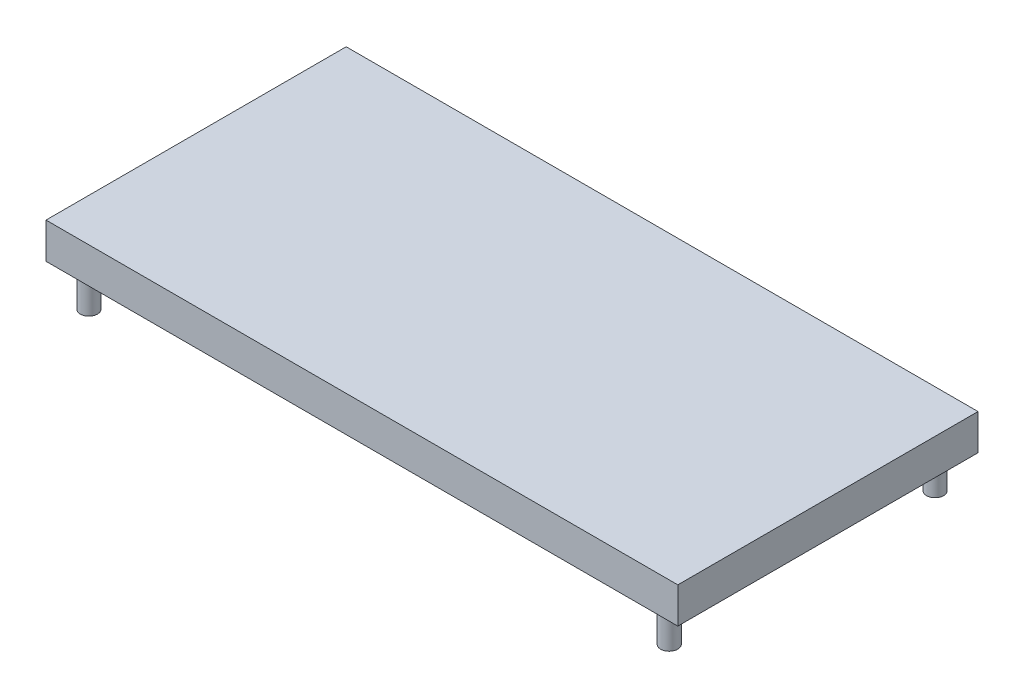
SolidWorks part; units mm, degrees
ref_plane "Front Plane" through (0, 0, 0) normal (0, 0, 1) x (1, 0, 0)
ref_plane "Top Plane" through (0, 0, 0) normal (0, 1, 0) x (1, 0, 0)
ref_plane "Right Plane" through (0, 0, 0) normal (1, 0, 0) x (0, 0, -1)
sketch "Sketch2" plane through (0, 0, 0) normal (0, 1, 0) x (1, 0, 0)
  line L1 (-110.5, 52.5) -> (110.5, 52.5)
  line L2 (-110.5, 52.5) -> (-110.5, -52.5)
  line L3 (-110.5, -52.5) -> (110.5, -52.5)
  line L4 (110.5, 52.5) -> (110.5, -52.5)
  dimension "D1" = 221
  dimension "D2" = 105
  dimension "D3" = 110.5
  dimension "D4" = 52.5
extrude "Boss-Extrude1" add sketch "Sketch2" along normal blind 2.5
sketch "Sketch3" plane through (0, 0, 0) normal (0, -1, 0) x (1, 0, 0)
  line L13 (110.5, -52.5) -> (-110.5, -52.5)
  line L14 (110.5, -52.5) -> (110.5, 52.5)
  line L15 (110.5, 52.5) -> (-110.5, 52.5)
  line L16 (-108, 50) -> (-108, -50)
  line L17 (108, 50) -> (-108, 50)
  line L18 (-108, -50) -> (108, -50)
  line L19 (108, -50) -> (108, 50)
  line L20 (-108, 50) -> (-108, -50)
  line L21 (108, 50) -> (-108, 50)
  line L22 (-108, -50) -> (108, -50)
  line L23 (108, -50) -> (108, 50)
  line L24 (-110.5, -52.5) -> (-110.5, 52.5)
  dimension "D1" = 2.5
extrude "Boss-Extrude2" add sketch "Sketch3" along normal blind 10
sketch "Sketch5" plane through (0, 0, 0) normal (0, -1, 0) x (1, 0, 0)
  line L0 (6.875, 0) -> (-6.875, 0) construction
  line L1 (101.5, -46.5) -> (-101.5, -46.5) construction
  line L2 (101.5, -46.5) -> (101.5, 46.5) construction
  line L3 (101.5, 46.5) -> (-101.5, 46.5) construction
  line L4 (-101.5, -46.5) -> (-101.5, 46.5) construction
  line L5 (0, -6.875) -> (0, 6.875) construction
  circle A0 centre (101.5, -46.5) radius 3
  circle A1 centre (-101.5, -46.5) radius 3
  circle A2 centre (-101.5, 46.5) radius 3
  circle A3 centre (101.5, 46.5) radius 3
  dimension "D5" = 6
  dimension "D1" = 203
  dimension "D2" = 93
  dimension "D3" = 46.5
  dimension "D4" = 101.5
extrude "Boss-Extrude3" add sketch "Sketch5" along normal blind 23
hole_wizard "M3 Tapped Hole1" positions "Sketch6" profile "Sketch7" tap size "M3" standard "ISO"
sketch "Sketch6" plane through (0, -23, 0) normal (0, -1, 0) x (-1, 0, 0)
  point P0 (-101.5, 46.5)
  point P3 (101.5, 46.5)
  point P6 (101.5, -46.5)
  point P9 (-101.5, -46.5)
sketch "Sketch7" plane through (101.5, -23, -46.5) normal (1, 0, 0) x (0, 0, -1)
  line L0 (0, 0) -> (0, 10.8511)
  line L1 (0, 10.8511) -> (1.25, 10.1)
  line L2 (1.25, 10.1) -> (1.25, 0)
  line L5 (1.25, 0) -> (0, 0)
  line L10 (0, 10.8511) -> (-1.25, 10.1) construction
  line L11 (0, -6.35) -> (0, 107.95) construction
  dimension "Tap Drill Dia." = 2.5
  dimension "Tap Drill Depth" = 10.1
  dimension "Drill Angle" = 118
cosmetic thread "Hole Thread1" parameters "D1"=6, "D2"=3
cosmetic thread "Hole Thread2" parameters "D1"=6, "D2"=3
cosmetic thread "Hole Thread3" parameters "D1"=6, "D2"=3
cosmetic thread "Hole Thread4" parameters "D1"=6, "D2"=3
equation "\"D3@Sketch2\"=\"D1@Sketch2\"/2"
equation "\"D4@Sketch2\"=\"D2@Sketch2\"/2"
equation "\"D3@Sketch5\"=\"D2@Sketch5\"/2"
equation "\"D4@Sketch5\"=\"D1@Sketch5\"/2"
